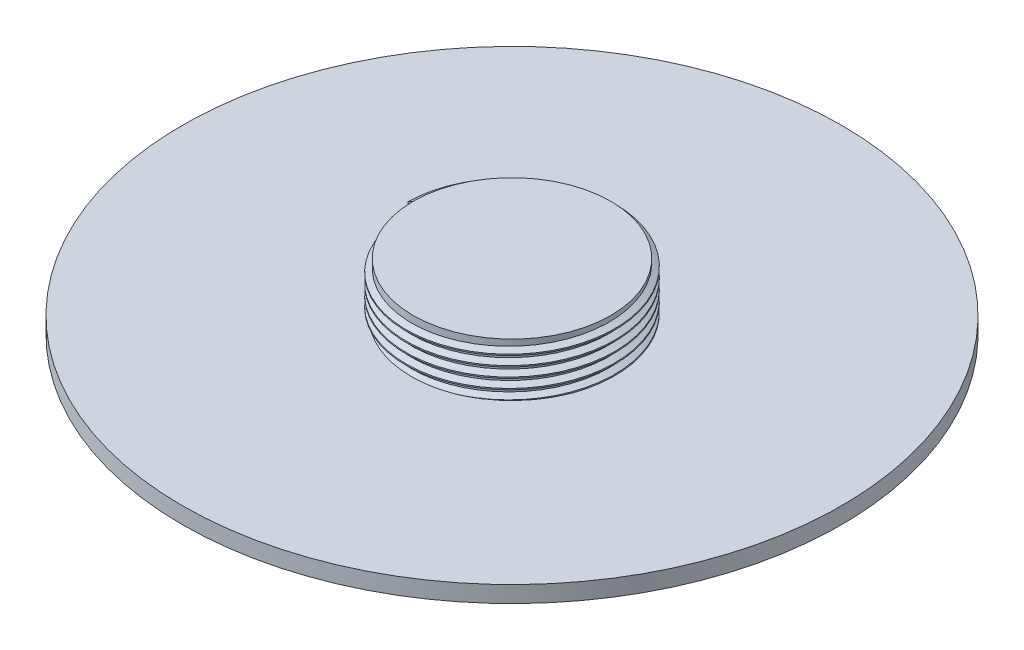
SolidWorks part; units mm, degrees
ref_plane "Front Plane" through (0, 0, 0) normal (0, 0, 1) x (1, 0, 0)
ref_plane "Top Plane" through (0, 0, 0) normal (0, 1, 0) x (1, 0, 0)
ref_plane "Right Plane" through (0, 0, 0) normal (1, 0, 0) x (0, 0, -1)
sketch "Sketch1" plane through (0, 0, 0) normal (0, 1, 0) x (1, 0, 0)
  circle A0 centre (0, 0) radius 50
  dimension "D1" = 100
extrude "Boss-Extrude1" add sketch "Sketch1" along normal blind 2.5
sketch "Sketch2" plane through (0, 2.5, 0) normal (0, 1, 0) x (1, 0, 0)
  circle A0 centre (0, 0) radius 15
  dimension "D1" = 30
extrude "Boss-Extrude2" add sketch "Sketch2" along normal blind 7.5
thread "Thread1" pitch 1.5 method extrude profile "Thread Profile1" start angle 0, offset 0, length 7.5, pitch 1.5, diameter 30
ref_plane "Plane1" through (-15, 10, 0) normal (0, 0, 1) x (-1, 0, 0)
sketch "Thread Profile1" plane through (-15, 10, 0) normal (0, 0, 1) x (-1, 0, 0)
  line L0 (0, 0) -> (0, 1.5) construction
  line L1 (0, 0) -> (0.8119, 0.4687)
  line L2 (0.8119, 0.4687) -> (0.8119, 0.6562)
  line L3 (0.8119, 0.6562) -> (0, 1.125)
  line L4 (0.8119, 0.5625) -> (0, 0.5625) construction
  line L11 (0, 0) -> (0, 1.125)
  point P2 (0, 0)
  dimension "Pitch" = 1.5
  dimension "Profile_Angle" = 60
  dimension "Profile_Land" = 0.1875
  dimension "Profile_Height" = 0.8119
